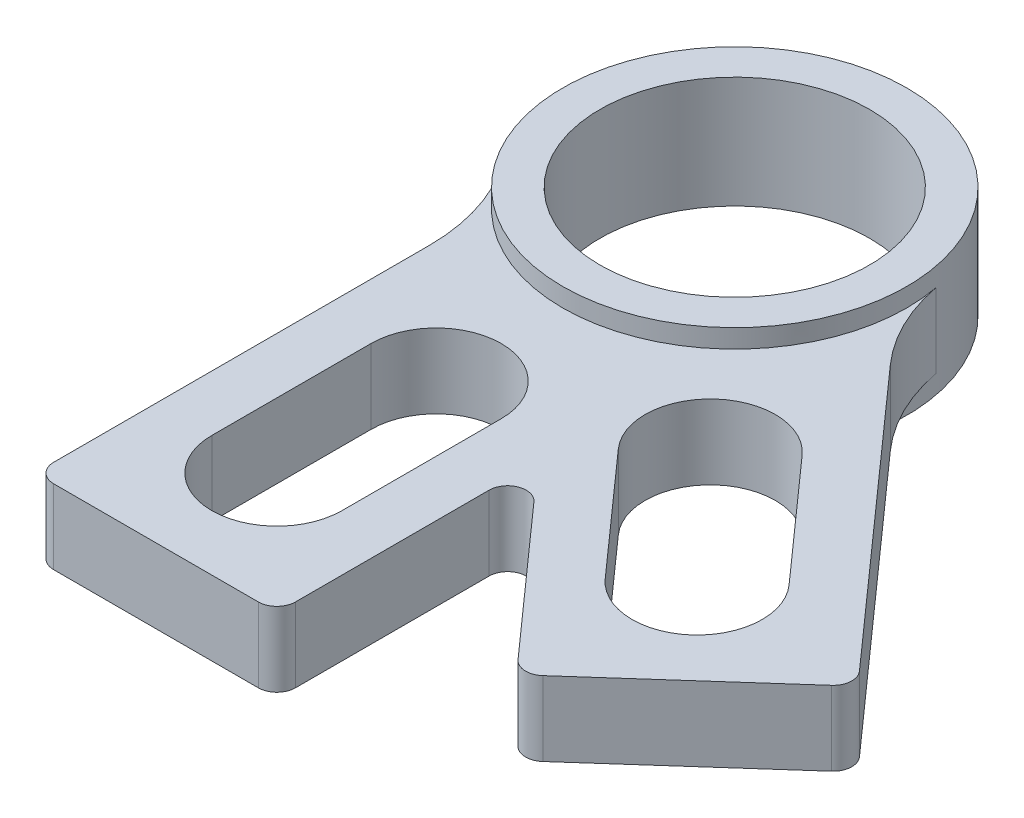
SolidWorks part; units mm, degrees
material "AISI 4130 Steel, annealed at 865C"
ref_plane "Front Plane" through (0, 0, 0) normal (0, 0, 1) x (1, 0, 0)
ref_plane "Top Plane" through (0, 0, 0) normal (0, 1, 0) x (1, 0, 0)
ref_plane "Right Plane" through (0, 0, 0) normal (1, 0, 0) x (0, 0, -1)
sketch "Sketch1" plane through (0, 0, 0) normal (0, 1, 0) x (1, 0, 0)
  line L0 (0, 0) -> (0, -49.3903) construction
  line L1 (0, 0) -> (32.8363, -36.8942) construction
  line L2 (0, -39.0716) -> (0, -25.4826) construction
  line L3 (-5.5562, -39.0716) -> (-5.5562, -25.4826)
  line L4 (5.5563, -39.0716) -> (5.5563, -25.4826)
  line L5 (25.976, -29.1862) -> (16.9416, -19.0353) construction
  line L6 (21.8256, -32.8801) -> (12.7911, -22.7292)
  line L7 (30.1265, -25.4922) -> (21.0921, -15.3413)
  line L8 (0, -49.3903) -> (0, -44.6278) construction
  line L9 (32.8363, -36.8942) -> (29.67, -33.3366) construction
  line L10 (-10.3187, -49.3903) -> (10.3188, -49.3903)
  line L11 (25.1282, -43.7544) -> (40.5443, -30.0339)
  line L12 (-10.3187, -49.3903) -> (-10.3187, -10.4432)
  line L13 (10.3188, -49.3903) -> (10.3188, -27.1148)
  line L14 (40.5443, -30.0339) -> (14.651, -0.9408)
  line L15 (25.1282, -43.7544) -> (10.3188, -27.1148)
  line L16 (196.1691, -220.4118) -> (13.8668, -15.5804) construction
  line L22 (0, 0) -> (10.3188, -27.1148) construction
  circle A0 centre (0, 0) radius 11.5062
  circle A1 centre (0, 0) radius 14.6812
  arc A2 (-5.5562, -39.0716) -> (5.5563, -39.0716) centre (0, -39.0716) ccw
  arc A3 (5.5563, -25.4826) -> (-5.5562, -25.4826) centre (0, -25.4826) ccw
  arc A4 (21.8256, -32.8801) -> (30.1265, -25.4922) centre (25.976, -29.1862) ccw
  arc A5 (21.0921, -15.3413) -> (12.7911, -22.7292) centre (16.9416, -19.0353) ccw
  point P8 (0, -32.2771)
  point P13 (21.4588, -24.1107)
  point P25 (0, -49.3903)
  point P27 (32.8363, -36.8942)
  dimension "D2" = 29.3624
  dimension "D3" = 4.7625
  dimension "D4" = 4.7625
  dimension "D5" = 13.589
  dimension "D6" = 49.3903
  dimension "D7" = 20.6375
extrude "Bearing_Insert_Extrude" add sketch "Sketch1" along normal mid plane 9.525 contours A1 A0 region at (-5.4988, 0, -13.1636)
extrude "Apex_Slot_Insert_Extrude" add sketch "Sketch1<4>" along normal mid plane 6.35 contours A1 L12 L10 L13 L15 L11 L14 A5 L7 A4 L6 A3 L4 A2 L3 region at (-9.6163, 0, 29.9168)
sketch "Sketch1<4>" plane through (0, 0, 0) normal (0, 1, 0) x (1, 0, 0) same geometry as "Sketch1"
fillet "Fillet1" radius 16.002 2 edges at (14.651, 0, 0.9408) (-10.3187, 0, 10.4432)
fillet "Fillet2" radius 1.5875 5 edges at (40.5443, 0, 30.0339) (25.1282, 0, 43.7544) (10.3188, 0, 27.1148) (10.3188, 0, 49.3903) (-10.3187, 0, 49.3903)
equation "\"Apex_thickness\"= .25"
equation "\"Bearing_diameter\"= 0.906in"
equation "\"A-arm_angle\"= 39.1893"
equation "\"D1@Sketch1\"=\"Bearing_diameter\""
equation "\"D1@Apex_Slot_Insert_Extrude\"=\"Apex_thickness\""
